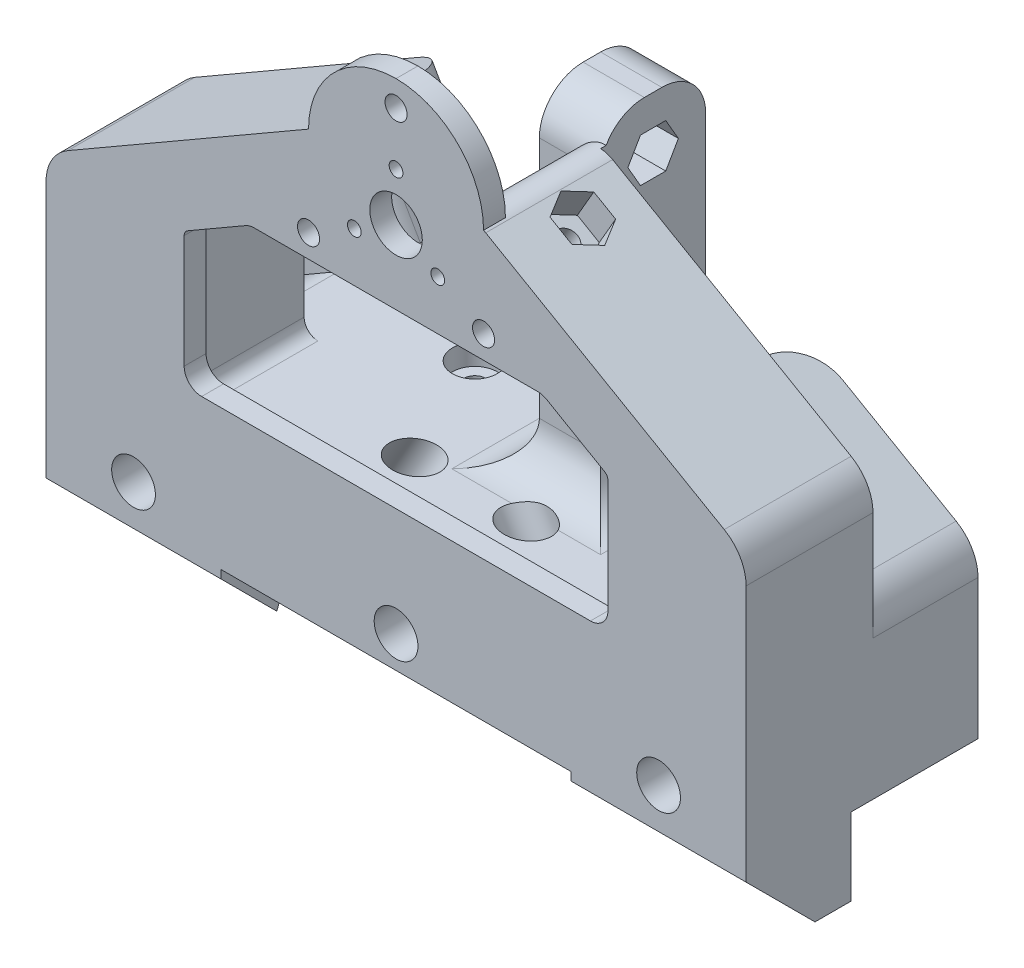
SolidWorks part; units mm, degrees
ref_plane "Front Plane" through (0, 0, 0) normal (0, 0, 1) x (1, 0, 0)
ref_plane "Top Plane" through (0, 0, 0) normal (0, 1, 0) x (1, 0, 0)
ref_plane "Right Plane" through (0, 0, 0) normal (1, 0, 0) x (0, 0, -1)
sketch "Sketch1" plane through (0, 0, 0) normal (0, 0, 1) x (1, 0, 0)
  line L0 (0, 0) -> (101.6, 0)
  line L2 (17.3289, 36.6882) -> (44.7508, 52.5202) construction
  line L3 (0, 23.9337) -> (0, 0)
  line L5 (101.6, 23.9337) -> (101.6, 0)
  line L6 (25.1187, 38.436) -> (29.5637, 30.737)
  line L7 (53.1812, 17.3346) -> (53.1812, 65.2727)
  line L8 (53.1812, 65.2727) -> (62.0712, 65.2727)
  line L9 (0, 23.9337) -> (25.1187, 38.436)
  line L10 (62.0712, 65.2727) -> (62.0712, 17.3346)
  line L11 (62.0712, 17.3346) -> (95.25, 17.3346)
  line L12 (44.7508, 52.5202) -> (56.8492, 52.5202) construction
  line L13 (50.8, -83.7726) -> (50.8, 0) construction
  line L14 (29.5637, 30.737) -> (6.35, 17.3346)
  line L15 (62.0712, 57.6527) -> (53.1812, 57.6527) construction
  line L16 (16.1383, 38.7504) -> (18.5196, 34.626) construction
  line L19 (17.3289, 36.6882) -> (12.7, 34.0157) construction
  line L20 (50.8, 39.3607) -> (50.8, 34.0157) construction
  line L21 (56.8492, 52.5202) -> (50.8, 62.9977) construction
  line L22 (50.8, 62.9977) -> (44.7508, 52.5202) construction
  line L23 (88.9, 34.0157) -> (12.7, 34.0157) construction
  line L25 (6.35, 17.3346) -> (53.1812, 17.3346)
  line L27 (72.0363, 30.737) -> (95.25, 17.3346)
  line L30 (101.6, 23.9337) -> (76.4813, 38.436)
  line L33 (76.4813, 38.436) -> (72.0363, 30.737)
  line L36 (56.8492, 52.5202) -> (145.4356, 1.3748) construction
  line L37 (44.7508, 52.5202) -> (50.8, 56.0127) construction
  line L38 (50.8, 56.0127) -> (56.8492, 52.5202) construction
  line L39 (50.8, 56.0127) -> (50.8, 62.9977) construction
  point P43 (50.8, -49.6476)
  dimension "D2" = 38.1
  dimension "D3" = 101.6
  dimension "D4" = 34.0157
  dimension "D5" = 6.35
  dimension "D6" = 5.3451
  dimension "D7" = 8.89
  dimension "D8" = 4.7625
  dimension "D9" = 4.7625
  dimension "D10" = 30
  dimension "D11" = 7.62
  dimension "D12" = 4.7625
  dimension "D13" = 6.985
  dimension "D14" = 7.62
  dimension "D15" = 5.3451
extrude "Boss-Extrude1" add sketch "Sketch1" along normal blind 15.24
sketch "Sketch5" plane through (35.7636, 61.9444, 0) normal (0.5, 0.866, 0) x (0, 0, -1)
  line L0 (-7.62, -47.0168) -> (-7.62, -54.6368) construction
  line L2 (-15.24, -47.0168) -> (0, -47.0168) construction
  circle A0 centre (-7.62, -54.6368) radius 1.5875
  dimension "D1" = 3.175
  dimension "D2" = 7.62
extrude "Cut-Extrude2" cut sketch "Sketch5" against normal up to surface (8.89 mm away) up to face at (83.6432, 24.0358, 7.62)
sketch "Sketch6" plane through (-10.3636, 17.9503, 0) normal (-0.5, 0.866, 0) x (0, 0, 1)
  line L0 (7.62, 40.9714) -> (7.62, 33.3514) construction
  line L2 (15.24, 40.9714) -> (0, 40.9714) construction
  circle A0 centre (7.62, 33.3514) radius 1.5875
  dimension "D2" = 3.175
  dimension "D1" = 7.62
extrude "Cut-Extrude3" cut sketch "Sketch6" against normal up to surface (8.89 mm away) up to face at (17.9568, 24.0358, 7.62)
sketch "Sketch11" plane through (62.0712, 0, 0) normal (-1, 0, 0) x (0, 0, 1)
  line L0 (7.62, 65.2727) -> (7.62, 57.6527) construction
  line L1 (7.62, 39.3607) -> (7.62, 17.3346) construction
  line L2 (15.24, 65.2727) -> (0, 65.2727) construction
  line L3 (15.24, 17.3346) -> (0, 17.3346) construction
  circle A0 centre (7.62, 57.6527) radius 1.5875
  circle A1 centre (7.62, 39.3607) radius 1.5875
  dimension "D1" = 3.175
  dimension "D2" = 7.62
  dimension "D3" = 22.0262
extrude "Cut-Extrude8" cut sketch "Sketch11" along normal up to next
sketch "Sketch7" plane through (0, 0, 15.24) normal (0, 0, 1) x (1, 0, 0)
  line L0 (101.6, 23.9337) -> (76.4813, 38.436) construction
  line L1 (0, 0) -> (101.6, 0)
  line L2 (0, 0) -> (0, 39.6983)
  line L3 (19.05, 17.3346) -> (50.8, 17.3346)
  line L4 (53.1812, 17.3346) -> (6.35, 17.3346) construction
  line L5 (45.5304, 55.7199) -> (19.05, 40.4315)
  line L8 (44.7508, 52.5202) -> (56.8492, 52.5202) construction
  line L9 (56.8492, 52.5202) -> (50.8, 62.9977) construction
  line L10 (38.9312, 51.9099) -> (40.1219, 49.8477) construction
  line L11 (50.8, 62.9977) -> (44.7508, 52.5202) construction
  line L12 (44.7508, 52.5202) -> (-5.7169, 23.3827) construction
  line L14 (50.8, 17.3346) -> (50.8, 0) construction
  line L15 (44.7508, 52.5202) -> (50.8, 56.0127) construction
  line L16 (50.8, 56.0127) -> (50.8, 62.9977) construction
  line L17 (50.8, 56.0127) -> (56.8492, 52.5202) construction
  line L18 (56.8492, 52.5202) -> (107.3169, 23.3827) construction
  line L20 (25.1187, 38.436) -> (0, 23.9337) construction
  line L21 (45.5304, 55.7199) -> (41.0854, 63.4189)
  line L22 (41.0854, 63.4189) -> (0, 39.6983)
  line L24 (50.8, 17.3346) -> (82.55, 17.3346)
  line L29 (95.25, 17.3346) -> (62.0712, 17.3346) construction
  line L32 (50.8, 62.9977) -> (50.8, 57.6527) construction
  line L36 (56.8492, 52.5202) -> (107.3169, 23.3827) construction
  line L42 (60.5146, 63.4189) -> (101.6, 39.6983)
  line L43 (56.0696, 55.7199) -> (60.5146, 63.4189)
  line L46 (56.0696, 55.7199) -> (82.55, 40.4315)
  line L47 (101.6, 0) -> (101.6, 39.6983)
  line L48 (19.05, 40.4315) -> (19.05, 17.3346)
  line L49 (82.55, 40.4315) -> (82.55, 17.3346)
  dimension "D1" = 6.985
  dimension "D2" = 8.89
  dimension "D5" = 5.3451
  dimension "D6" = 7.62
  dimension "D7" = 2.3813
  dimension "D8" = 5.3451
  dimension "D9" = 2.3813
  dimension "D10" = 19.05
  dimension "D11" = 2.3813
extrude "Boss-Extrude4" add sketch "Sketch7" along normal blind 15.24
sketch "Sketch8" plane through (-12.7448, 22.0747, 0) normal (0.5, -0.866, 0) x (0, 0, -1)
  line L0 (-22.86, 67.2904) -> (-22.86, 59.6704) construction
  line L1 (-15.24, 67.2904) -> (-15.24, 19.8491) construction
  line L3 (-30.48, 67.2904) -> (-15.24, 67.2904) construction
  circle A0 centre (-22.86, 59.6704) radius 1.5875
  dimension "D2" = 3.175
  dimension "D1" = 7.62
  dimension "D3" = 7.62
extrude "Cut-Extrude4" cut sketch "Sketch8" against normal blind 12.7
sketch "Sketch9" plane through (38.1448, 66.0688, 0) normal (-0.5, -0.866, 0) x (0, 0, 1)
  line L0 (22.86, -20.6978) -> (22.86, -28.3178) construction
  line L1 (15.24, -68.1391) -> (15.24, -22.4952) construction
  line L2 (30.48, -20.6978) -> (15.24, -20.6978) construction
  circle A0 centre (22.86, -28.3178) radius 1.5875
  dimension "D1" = 3.175
  dimension "D2" = 7.62
  dimension "D3" = 7.62
extrude "Cut-Extrude5" cut sketch "Sketch9" against normal blind 12.7
sketch "Sketch13" plane through (0, 0, 30.48) normal (0, 0, 1) x (1, 0, 0)
  line L0 (38.9312, 51.9099) -> (40.1219, 49.8477) construction
  line L1 (19.05, 40.4315) -> (45.5304, 55.7199) construction
  line L5 (37.5564, 51.1162) -> (40.3061, 52.7037) construction
  line L6 (44.7508, 52.5202) -> (40.1219, 49.8477) construction
  line L8 (50.8, 62.9977) -> (44.7508, 52.5202) construction
  line L9 (44.7508, 52.5202) -> (56.8492, 52.5202) construction
  line L10 (56.8492, 52.5202) -> (50.8, 62.9977) construction
  line L11 (44.7508, 52.5202) -> (50.8, 56.0127) construction
  line L12 (50.8, 56.0127) -> (50.8, 62.9977) construction
  line L13 (56.8492, 52.5202) -> (50.8, 56.0127) construction
  dimension "D1" = 6.985
  dimension "D2" = 2.3813
  dimension "D3" = 5.3451
sketch "Sketch14" plane through (0, 0, 0) normal (0, 0, -1) x (-1, 0, 0)
  line L0 (-83.0804, 34.626) -> (-85.4617, 38.7504) construction
  line L1 (-50.8, 34.0157) -> (-50.8, 56.0127) construction
  line L2 (-84.2711, 36.6882) -> (-88.9, 34.0157) construction
  line L3 (-88.9, 34.0157) -> (-50.8, 34.0157) construction
  line L5 (-50.8, 34.0157) -> (-12.7, 34.0157) construction
  line L6 (-76.4813, 38.436) -> (-72.0363, 30.737) construction
  line L7 (-101.6, 23.9337) -> (-82.55, 34.9322) construction
  dimension "D1" = 5.3451
  dimension "D2" = 4.7625
  dimension "D3" = 7.62
sketch "Sketch15" plane through (42.5898, 73.7678, 0) normal (0.5, 0.866, 0) x (0, 0, -1)
  line L0 (-22.86, -28.3178) -> (-19.685, -28.3178) construction
  line L1 (-19.685, -26.4847) -> (-19.685, -30.1509)
  line L2 (-19.685, -26.4847) -> (-22.86, -24.6516)
  line L3 (-22.86, -24.6516) -> (-26.035, -26.4847)
  line L4 (-26.035, -26.4847) -> (-26.035, -30.1509)
  line L5 (-26.035, -30.1509) -> (-22.86, -31.984)
  line L6 (-22.86, -31.984) -> (-19.685, -30.1509)
  line L7 (-21.2725, -25.5681) -> (-22.86, -28.3178) construction
  line L8 (-22.86, -28.3178) -> (-24.4475, -31.0674) construction
  dimension "D1" = 6.35
extrude "Cut-Extrude9" cut sketch "Sketch15" against normal blind 4.7625
sketch "Sketch16" plane through (31.3186, 54.2454, 0) normal (0.5, 0.866, 0) x (0, 0, -1)
  line L0 (-7.62, -54.6368) -> (-4.445, -54.6368) construction
  line L1 (-4.445, -52.8037) -> (-4.445, -56.4699)
  line L2 (-4.445, -52.8037) -> (-7.62, -50.9706)
  line L3 (-7.62, -50.9706) -> (-10.795, -52.8037)
  line L4 (-10.795, -52.8037) -> (-10.795, -56.4699)
  line L5 (-10.795, -56.4699) -> (-7.62, -58.3029)
  line L6 (-7.62, -58.3029) -> (-4.445, -56.4699)
  line L7 (-6.0325, -51.8871) -> (-7.62, -54.6368) construction
  line L8 (-7.62, -54.6368) -> (-9.2075, -57.3864) construction
  circle A0 centre (-7.62, -54.6368) radius 1.5875 construction
  dimension "D1" = 6.35
extrude "Cut-Extrude10" cut sketch "Sketch16" along normal blind 4.7625
sketch "Sketch17" plane through (-5.9186, 10.2513, 18.8617) normal (-0.5, 0.866, 0) x (-0.2962, -0.171, 0.9397)
  line L0 (-21.9706, 27.4952) -> (-18.7956, 27.4952) construction
  line L1 (-18.7956, 29.3283) -> (-18.7956, 25.6621)
  line L2 (-18.7956, 29.3283) -> (-21.9706, 31.1614)
  line L3 (-21.9706, 31.1614) -> (-25.1456, 29.3283)
  line L4 (-25.1456, 29.3283) -> (-25.1456, 25.6621)
  line L5 (-25.1456, 25.6621) -> (-21.9706, 23.829)
  line L6 (-21.9706, 23.829) -> (-18.7956, 25.6621)
  line L7 (-20.3831, 30.2448) -> (-21.9706, 27.4952) construction
  line L8 (-21.9706, 27.4952) -> (-23.5581, 24.7456) construction
  circle A2 centre (-21.9706, 27.4952) radius 1.5875 construction
  dimension "D1" = 6.35
extrude "Cut-Extrude11" cut sketch "Sketch17" along normal blind 4.7625
sketch "Sketch20" plane through (62.0712, 0, -63.5) normal (-1, 0, 0) x (0, 0, 1)
  line L0 (71.12, 39.3607) -> (73.8696, 37.7732) construction
  line L1 (74.7862, 39.3607) -> (72.9531, 36.1857)
  line L2 (74.7862, 39.3607) -> (72.9531, 42.5357)
  line L3 (72.9531, 42.5357) -> (69.2869, 42.5357)
  line L4 (69.2869, 42.5357) -> (67.4538, 39.3607)
  line L5 (67.4538, 39.3607) -> (69.2869, 36.1857)
  line L6 (69.2869, 36.1857) -> (72.9531, 36.1857)
  line L7 (73.8696, 40.9482) -> (71.12, 39.3607) construction
  line L8 (71.12, 39.3607) -> (68.3704, 37.7732) construction
  line L9 (74.7862, 57.6527) -> (72.9531, 54.4777)
  line L10 (74.7862, 57.6527) -> (72.9531, 60.8277)
  line L11 (72.9531, 60.8277) -> (69.2869, 60.8277)
  line L12 (69.2869, 60.8277) -> (67.4538, 57.6527)
  line L13 (67.4538, 57.6527) -> (69.2869, 54.4777)
  line L14 (69.2869, 54.4777) -> (72.9531, 54.4777)
  line L15 (71.12, 57.6527) -> (73.8696, 56.0652) construction
  line L16 (73.8696, 59.2402) -> (71.12, 57.6527) construction
  line L17 (71.12, 57.6527) -> (68.3704, 56.0652) construction
  dimension "D1" = 6.35
  dimension "D3" = 60
  dimension "D2" = 2
extrude "Cut-Extrude13" cut sketch "Sketch20" along normal blind 4.7625
sketch "Sketch21" plane through (-66.0998, 1.5355, 0) normal (0.5, -0.866, 0) x (0.866, 0.5, 0)
  line L0 (116.1468, 22.86) -> (119.3218, 22.86) construction
  line L1 (119.3218, 24.6931) -> (119.3218, 21.0269)
  line L2 (119.3218, 24.6931) -> (116.1468, 26.5262)
  line L3 (116.1468, 26.5262) -> (112.9718, 24.6931)
  line L4 (112.9718, 24.6931) -> (112.9718, 21.0269)
  line L5 (112.9718, 21.0269) -> (116.1468, 19.1938)
  line L6 (116.1468, 19.1938) -> (119.3218, 21.0269)
  line L7 (117.7343, 25.6096) -> (116.1468, 22.86) construction
  line L8 (116.1468, 22.86) -> (114.5593, 20.1104) construction
  circle A0 centre (116.1468, 22.86) radius 1.5875 construction
  dimension "D1" = 6.35
extrude "Cut-Extrude16" cut sketch "Sketch21" along normal blind 4.7625
sketch "Sketch23" plane through (0, 0, 30.48) normal (0, 0, 1) x (1, 0, 0)
  line L0 (44.7508, 52.5202) -> (50.8, 56.0127) construction
  line L1 (50.8, 56.0127) -> (50.8, 62.9977) construction
  line L2 (50.8, 56.0127) -> (56.8492, 52.5202) construction
  line L3 (38.1, 61.6953) -> (0, 39.6983)
  line L4 (63.5, 61.6953) -> (101.6, 39.6983)
  line L5 (101.6, 39.6983) -> (101.6, 0)
  line L6 (101.6, 0) -> (0, 0)
  line L7 (0, 0) -> (0, 39.6983)
  line L8 (41.0854, 63.4189) -> (0, 39.6983) construction
  line L9 (101.6, 0) -> (101.6, 39.6983) construction
  line L10 (101.6, 39.6983) -> (60.5146, 63.4189) construction
  line L11 (50.8, 74.3953) -> (50.8, 62.9977) construction
  line L13 (63.5, 61.6953) -> (63.5, 74.3953)
  line L14 (63.5, 74.3953) -> (38.1, 74.3953)
  line L15 (38.1, 61.6953) -> (38.1, 74.3953)
  circle A1 centre (50.8, 56.0127) radius 3.81
  point P11 (50.8, 69.0276)
  dimension "D1" = 7.62
  dimension "D2" = 25.4
  dimension "D3" = 12.7
extrude "Boss-Extrude5" add sketch "Sketch23" along normal blind 3.175
hole_wizard "M3 Clearance Hole1" positions "Sketch26" profile "Sketch25" hole size "M3" standard "Ansi Metric"
sketch "Sketch26" plane through (0, 0, 33.655) normal (0, 0, 1) x (1, 0, 0)
  line L0 (50.8, 70.6774) -> (38.1, 48.6804) construction
  line L1 (38.1, 48.6804) -> (63.5, 48.6804) construction
  line L2 (63.5, 48.6804) -> (50.8, 70.6774) construction
  line L4 (38.1, 48.6804) -> (50.8, 56.0127) construction
  line L5 (50.8, 56.0127) -> (50.8, 0) construction
  line L8 (50.8, 56.0127) -> (63.5, 48.6804) construction
  line L10 (50.8, 56.0127) -> (50.8, 70.6774) construction
  line L12 (0, 0) -> (101.6, 0) construction
  circle A1 centre (50.8, 56.0127) radius 3.81 construction
  point P0 (38.1, 48.6804)
  point P1 (63.5, 48.6804)
  point P3 (50.8, 70.6774)
  dimension "D1" = 25.4
sketch "Sketch25" plane through (38.1, 48.6804, 33.655) normal (1, 0, 0) x (0, -1, 0)
  line L0 (0, 0) -> (0, 10.8674)
  line L1 (0, 10.8674) -> (1.6, 9.906)
  line L2 (1.6, 9.906) -> (1.6, 0)
  line L5 (1.6, 0) -> (0, 0)
  line L10 (0, 10.8674) -> (-1.6, 9.906) construction
  line L11 (0, -6.35) -> (0, 107.95) construction
  dimension "Hole Dia." = 3.2
  dimension "Hole Depth" = 9.906
  dimension "Drill Angle" = 118
sketch "Sketch27" plane through (0, 0, 33.655) normal (0, 0, 1) x (1, 0, 0)
  circle A0 centre (44.7508, 52.5202) radius 1
  circle A1 centre (56.8492, 52.5202) radius 1
  circle A2 centre (50.8, 62.9977) radius 1
  dimension "D1" = 2
extrude "Cut-Extrude18" cut sketch "Sketch27" against normal up to next
sketch "Sketch22" plane through (0, 0, 0) normal (0, 0, -1) x (-1, 0, 0)
  line L0 (-50.8, 0) -> (-50.8, 4.6346) construction
  line L1 (0, 0) -> (-101.6, 0) construction
  line L2 (-50.8, 4.6346) -> (-88.9, 4.6346) construction
  line L3 (-50.8, 4.6346) -> (-12.7, 4.6346) construction
  line L4 (-95.25, 17.3346) -> (-62.0712, 17.3346) construction
  circle A0 centre (-88.9, 4.6346) radius 3.175
  circle A1 centre (-50.8, 4.6346) radius 3.175
  circle A2 centre (-12.7, 4.6346) radius 3.175
  dimension "D1" = 6.35
  dimension "D2" = 38.1
  dimension "D3" = 12.7
extrude "Cut-Extrude17" cut sketch "Sketch22" against normal through all
hole_wizard "CBORE for M3 SHCS1" positions "Sketch29" profile "Sketch28" counterbore size "M3" standard "Ansi Metric" end condition through all
sketch "Sketch29" plane through (-15.7257, 17.3346, 0.8913) normal (0, -1, 0) x (1, 0, 0)
  line L0 (50.6507, 5.4587) -> (82.4007, 5.4587) construction
  line L2 (66.5257, 5.4587) -> (66.5257, -0.8913) construction
  line L4 (15.7257, -0.8913) -> (117.3257, -0.8913) construction
  line L5 (66.5257, -0.8913) -> (28.4257, -0.8913) construction
  point P0 (82.4007, 5.4587)
  point P1 (50.6507, 5.4587)
  dimension "D1" = 6.35
  dimension "D2" = 31.75
sketch "Sketch28" plane through (66.675, 17.3346, 6.35) normal (1, 0, 0) x (0, 0, 1)
  line L0 (0, 0) -> (0, 17.3346)
  line L1 (0, 17.3346) -> (1.6, 17.3346)
  line L3 (1.6, 17.3346) -> (1.6, 3)
  line L4 (1.6, 3) -> (3.25, 3)
  line L5 (3.25, 3) -> (3.25, 0)
  line L7 (3.25, 0) -> (0, 0)
  line L11 (0, -6.35) -> (0, 107.95) construction
  dimension "Thru Hole Dia." = 3.2
  dimension "Thru Hole Depth" = 17.3346
  dimension "C'Bore Dia." = 6.5
  dimension "C'Bore Depth" = 3
sketch "Sketch31" plane through (0, 0, 0) normal (0, -1, 0) x (1, 0, 0)
  line L0 (25.4, 18.415) -> (76.2, 18.415) construction
  line L1 (0, 33.655) -> (25.4, 33.655)
  line L2 (0, 33.655) -> (0, 18.415)
  line L3 (0, 18.415) -> (25.4, 18.415)
  line L4 (25.4, 33.655) -> (25.4, 18.415)
  line L5 (101.6, 33.655) -> (76.2, 33.655)
  line L6 (101.6, 33.655) -> (101.6, 18.415)
  line L7 (101.6, 18.415) -> (76.2, 18.415)
  line L8 (76.2, 33.655) -> (76.2, 18.415)
  line L9 (50.8, 18.415) -> (50.8, 33.655) construction
  line L10 (0, 33.655) -> (101.6, 33.655) construction
  dimension "D1" = 50.8
  dimension "D2" = 15.24
extrude "Boss-Extrude7" add sketch "Sketch31" along normal blind 11.2
fillet "Fillet10" radius 2 7 edges at (82.55, 40.4315, 22.86) (19.05, 40.4315, 22.86) (50.8, 17.3346, 30.48) (95.25, 17.3346, 7.62) (6.35, 17.3346, 7.62)
fillet "Fillet11" radius 6.35 14 edges at (43.3079, 59.5694, 15.24) (74.2588, 34.5865, 15.24) (27.3412, 34.5865, 15.24) (27.3412, 34.5865, 0) (74.2588, 34.5865, 0) (101.6, 39.6983, 24.4475) (0, 39.6983, 24.4475) (57.6262, 65.2727, 15.24) (57.6262, 65.2727, 0)
sketch "Sketch33" plane through (38.1448, 66.0688, 0) normal (-0.5, -0.866, 0) x (0.866, -0.5, 0)
  circle A0 centre (28.3178, 22.86) radius 3.175
  dimension "D1" = 6.35
extrude "Cut-Extrude19" cut sketch "Sketch33" along normal through all
sketch "Sketch34" plane through (-12.7448, 22.0747, 0) normal (0.5, -0.866, 0) x (0.866, 0.5, 0)
  circle A0 centre (59.6704, 22.86) radius 3.175
  dimension "D1" = 6.35
extrude "Cut-Extrude20" cut sketch "Sketch34" along normal through all
fillet "Fillet12" radius 12.7 2 edges at (38.1, 74.3953, 32.0675) (63.5, 74.3953, 32.0675)
fillet "Fillet13" radius 3.81 2 edges at (56.0696, 55.7199, 22.86) (60.5146, 63.4189, 21.927)
sketch "Sketch35" plane through (0, 0, 30.48) normal (0, 0, -1) x (-1, 0, 0)
  line L8 (-41.4514, 64.7849) -> (-39.2414, 63.509)
  line L9 (-72.0491, 45.3395) -> (-29.5509, 45.3395)
  line L10 (-72.0491, 45.3395) -> (-81.05, 40.1428)
  line L11 (-81.55, 39.2768) -> (-81.55, 20.3346)
  line L12 (-81.55, 20.3346) -> (-20.05, 20.3346)
  line L13 (-20.05, 20.3346) -> (-20.05, 39.2768)
  line L14 (-20.55, 40.1428) -> (-29.5509, 45.3395)
  line L16 (-41.0854, 63.4189) -> (-38.1, 61.6953)
  line L17 (-58.6096, 60.1193) -> (-57.9746, 59.0195)
  line L18 (-59.3692, 53.8149) -> (-81.55, 41.0088)
  line L19 (-82.55, 39.2768) -> (-82.55, 19.3346)
  line L20 (-82.55, 19.3346) -> (-19.05, 19.3346)
  line L21 (-19.05, 19.3346) -> (-19.05, 39.2768)
  line L22 (-20.05, 41.0088) -> (-45.5304, 55.7199)
  line L23 (-45.5304, 55.7199) -> (-41.0854, 63.4189)
  line L24 (-41.0854, 63.4189) -> (-38.1, 61.6953) construction
  line L25 (-58.6096, 60.1193) -> (-57.9746, 59.0195) construction
  line L26 (-59.3692, 53.8149) -> (-81.55, 41.0088) construction
  line L27 (-82.55, 39.2768) -> (-82.55, 19.3346) construction
  line L28 (-82.55, 19.3346) -> (-19.05, 19.3346) construction
  line L29 (-19.05, 19.3346) -> (-19.05, 39.2768) construction
  line L30 (-20.05, 41.0088) -> (-45.5304, 55.7199) construction
  line L31 (-45.5304, 55.7199) -> (-41.0854, 63.4189) construction
  line L32 (-57.7436, 60.6193) -> (-57.1086, 59.5195) construction
  line L33 (-46.8964, 55.3539) -> (-41.4514, 64.7849) construction
  line L34 (-20.55, 40.1428) -> (-46.8964, 55.3539) construction
  line L35 (-58.8692, 52.9489) -> (-81.05, 40.1428) construction
  circle A6 centre (-38.1, 48.6804) radius 1.6 construction
  arc A10 (-81.05, 40.1428) -> (-81.55, 39.2768) centre (-80.55, 39.2768) ccw
  arc A11 (-20.05, 39.2768) -> (-20.55, 40.1428) centre (-21.05, 39.2768) ccw
  arc A12 (-38.1, 61.6953) -> (-50.8, 74.3953) centre (-50.8, 61.6953) ccw
  arc A13 (-50.8, 74.3953) -> (-63.5, 61.6763) centre (-50.8, 61.6953) ccw
  arc A14 (-58.6096, 60.1193) -> (-63.5, 61.6763) centre (-61.9092, 58.2143) ccw
  arc A15 (-59.3692, 53.8149) -> (-57.9746, 59.0195) centre (-61.2742, 57.1145) ccw
  arc A16 (-81.55, 41.0088) -> (-82.55, 39.2768) centre (-80.55, 39.2768) ccw
  arc A17 (-19.05, 39.2768) -> (-20.05, 41.0088) centre (-21.05, 39.2768) ccw
  arc A18 (-38.1, 61.6953) -> (-50.8, 74.3953) centre (-50.8, 61.6953) ccw construction
  arc A19 (-50.8, 74.3953) -> (-63.5, 61.6763) centre (-50.8, 61.6953) ccw construction
  arc A20 (-58.6096, 60.1193) -> (-63.5, 61.6763) centre (-61.9092, 58.2143) ccw construction
  arc A21 (-59.3692, 53.8149) -> (-57.9746, 59.0195) centre (-61.2742, 57.1145) ccw construction
  arc A22 (-81.55, 41.0088) -> (-82.55, 39.2768) centre (-80.55, 39.2768) ccw construction
  arc A23 (-19.05, 39.2768) -> (-20.05, 41.0088) centre (-21.05, 39.2768) ccw construction
  arc A24 (-50.8, 73.3953) -> (-62.4274, 62.9963) centre (-50.8, 61.6953) ccw construction
  arc A25 (-39.2414, 63.509) -> (-50.8, 73.3953) centre (-50.8, 61.6953) ccw construction
  arc A26 (-57.7436, 60.6193) -> (-62.4274, 62.9963) centre (-61.9092, 58.2143) ccw construction
  arc A27 (-58.8692, 52.9489) -> (-57.1086, 59.5195) centre (-61.2742, 57.1145) ccw construction
  dimension "D3" = 3.3409
  dimension "D1" = 0
  dimension "D2" = 1
extrude "Cut-Extrude21" cut sketch "Sketch35" against normal through all contours L13 L14 L10 L11 L12 region at (50.8, 32.4621, 30.48)
fillet "Fillet14" radius 2.54 4 edges at (81.55, 20.3346, 32.0675) (20.05, 20.3346, 32.0675) (29.5509, 45.3395, 32.0675) (72.0491, 45.3395, 32.0675)
chamfer "Chamfer1" distance 10 angle 45 2 edges at (88.9, -11.2, 33.655) (12.7, -11.2, 33.655)
